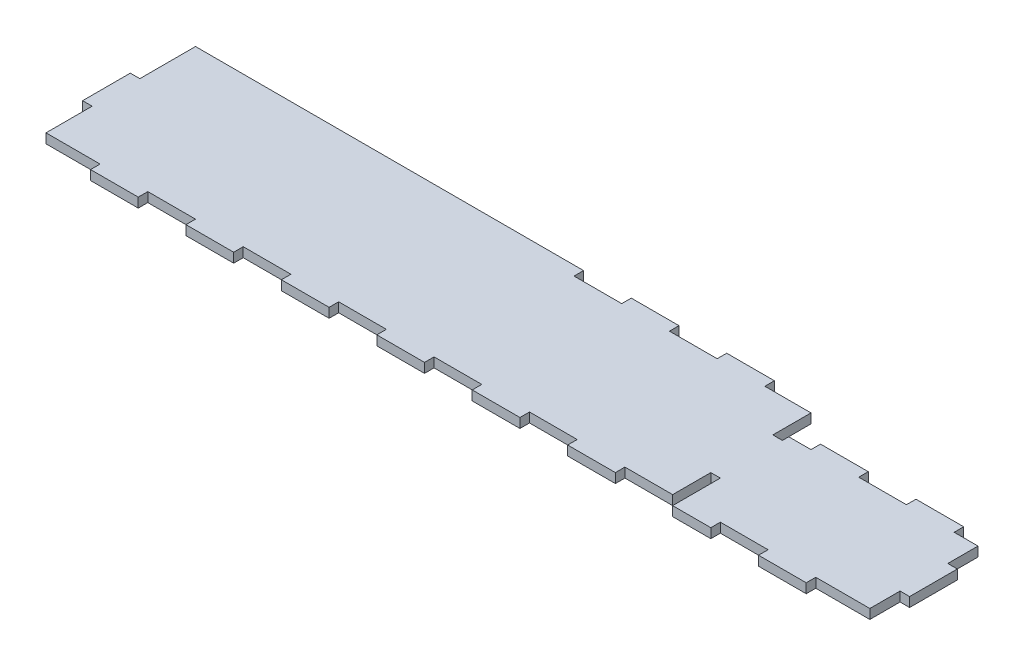
SolidWorks part; units mm, degrees
ref_plane "Alzado" through (0, 0, 0) normal (0, 0, 1) x (1, 0, 0)
ref_plane "Planta" through (0, 0, 0) normal (0, 1, 0) x (1, 0, 0)
ref_plane "Vista lateral" through (0, 0, 0) normal (1, 0, 0) x (0, 0, -1)
sketch "Croquis1" plane through (0, 0, 0) normal (0, 1, 0) x (1, 0, 0)
  line L0 (125, 50) -> (3, 50)
  line L1 (20, 50) -> (35, 50)
  line L2 (197, 3) -> (200, 3)
  line L3 (20, 0) -> (35, 0)
  line L4 (265, 12.5) -> (265, 27.5)
  line L5 (254.5, 40) -> (239.5, 40)
  line L6 (0, 25) -> (0, 32.5)
  line L7 (0, 32.5) -> (3, 32.5)
  line L8 (3, 32.5) -> (3, 47)
  line L9 (200, 15) -> (203, 15)
  line L10 (110, 47) -> (95, 47) construction
  line L11 (95, 47) -> (95, 50) construction
  line L12 (95, 50) -> (80, 50)
  line L13 (80, 50) -> (80, 47) construction
  line L14 (80, 47) -> (65, 47) construction
  line L15 (65, 47) -> (65, 50) construction
  line L16 (65, 50) -> (50, 50)
  line L17 (50, 50) -> (50, 47) construction
  line L18 (50, 47) -> (35, 47) construction
  line L19 (35, 47) -> (35, 50) construction
  line L20 (35, 50) -> (20, 50)
  line L21 (20, 50) -> (20, 47) construction
  line L22 (20, 47) -> (3, 47) construction
  line L23 (185, 47) -> (196.5, 47)
  line L24 (185, 50) -> (185, 47)
  line L25 (170, 47) -> (170, 50)
  line L26 (155, 47) -> (170, 47)
  line L27 (155, 50) -> (155, 47)
  line L28 (140, 47) -> (140, 50)
  line L29 (125, 47) -> (140, 47)
  line L30 (125, 50) -> (125, 47)
  line L31 (110, 47) -> (110, 50) construction
  line L32 (0, 25) -> (0, 17.5)
  line L33 (203, 15) -> (203, 0)
  line L34 (0, 17.5) -> (3, 17.5)
  line L35 (3, 17.5) -> (3, 3)
  line L36 (224.5, 40) -> (209.5, 40)
  line L37 (140, 3) -> (125, 3)
  line L38 (125, 3) -> (125, 0)
  line L39 (125, 0) -> (110, 0)
  line L40 (110, 0) -> (110, 3)
  line L41 (110, 3) -> (95, 3)
  line L42 (95, 3) -> (95, 0)
  line L43 (95, 0) -> (80, 0)
  line L44 (80, 0) -> (80, 3)
  line L45 (80, 3) -> (65, 3)
  line L46 (65, 3) -> (65, 0)
  line L47 (65, 0) -> (50, 0)
  line L48 (50, 0) -> (50, 3)
  line L49 (50, 3) -> (35, 3)
  line L50 (35, 3) -> (35, 0)
  line L51 (35, 0) -> (20, 0)
  line L52 (20, 0) -> (20, 3)
  line L53 (20, 3) -> (3, 3)
  line L54 (245, 3) -> (262, 3)
  line L55 (245, 0) -> (245, 3)
  line L56 (230, 3) -> (230, 0)
  line L57 (215, 3) -> (230, 3)
  line L58 (215, 0) -> (215, 3)
  line L59 (3, 50) -> (3, 47)
  line L60 (185, 3) -> (197, 3)
  line L61 (185, 0) -> (185, 3)
  line L62 (170, 3) -> (170, 0)
  line L63 (155, 3) -> (170, 3)
  line L64 (155, 0) -> (155, 3)
  line L65 (140, 3) -> (140, 0)
  line L66 (254.5, 40) -> (239.5, 40)
  line L67 (199.5, 35) -> (202.5, 35)
  line L68 (224.5, 37) -> (239.5, 37)
  line L69 (239.5, 37) -> (239.5, 40)
  line L70 (239.5, 40) -> (254.5, 40)
  line L71 (254.5, 40) -> (254.5, 37)
  line L72 (254.5, 37) -> (262, 37)
  line L73 (209.5, 37) -> (202.5, 37)
  line L74 (209.5, 40) -> (209.5, 37)
  line L75 (224.5, 37) -> (224.5, 40)
  line L76 (202.5, 35) -> (202.5, 37)
  line L78 (265, 20) -> (265, 27.5)
  line L79 (265, 27.5) -> (262, 27.5)
  line L80 (262, 27.5) -> (262, 37)
  line L81 (265, 20) -> (265, 12.5)
  line L82 (265, 12.5) -> (262, 12.5)
  line L83 (262, 12.5) -> (262, 3)
  line L85 (196.5, 47) -> (199.5, 47)
  line L87 (199.5, 35) -> (199.5, 37)
  line L89 (200, 15) -> (200, 3)
  line L90 (0, 17.5) -> (0, 32.5)
  line L91 (50, 0) -> (65, 0)
  line L92 (80, 0) -> (95, 0)
  line L93 (110, 0) -> (125, 0)
  line L94 (140, 0) -> (155, 0)
  line L95 (170, 0) -> (185, 0)
  line L96 (203, 0) -> (215, 0)
  line L97 (230, 0) -> (245, 0)
  line L98 (170, 50) -> (185, 50)
  line L99 (140, 50) -> (155, 50)
  line L100 (50, 50) -> (65, 50)
  line L101 (80, 50) -> (95, 50)
  line L102 (110, 50) -> (125, 50)
  line L103 (199.5, 47) -> (199.5, 37)
  dimension "D3" = 17
  dimension "D4" = 3
  dimension "D5" = 7.5
  dimension "D6" = 3
  dimension "D7" = 11.5
  dimension "D9" = 15
  dimension "D10" = 15
  dimension "D11" = 15
  dimension "D12" = 15
  dimension "D13" = 15
  dimension "D14" = 7.5
  dimension "D17" = 15
  dimension "D18" = 15
  dimension "D19" = 15
  dimension "D20" = 15
  dimension "D21" = 15
  dimension "D22" = 15
  dimension "D23" = 15
  dimension "D26" = 15
  dimension "D27" = 7.5
  dimension "D28" = 3
  dimension "D29" = 7.5
extrude "Saliente-Extruir1" add sketch "Croquis1" along normal blind 3 contours L102 L31 L10 L11 L12 L13 L14 L15 L16 L17 L18 L19 L1 L21 L22 L8 L7 L6 L32 L34 L35 L53 L52 L3 L50 L49 L48 L47 L46 L45 L44 L43 L42 L41 L40 L39 L38 L37 L65 L94 L64 L63 L62 L95 L61 L60 L89 L96 region at (125.8136, 0, -24.4318)
